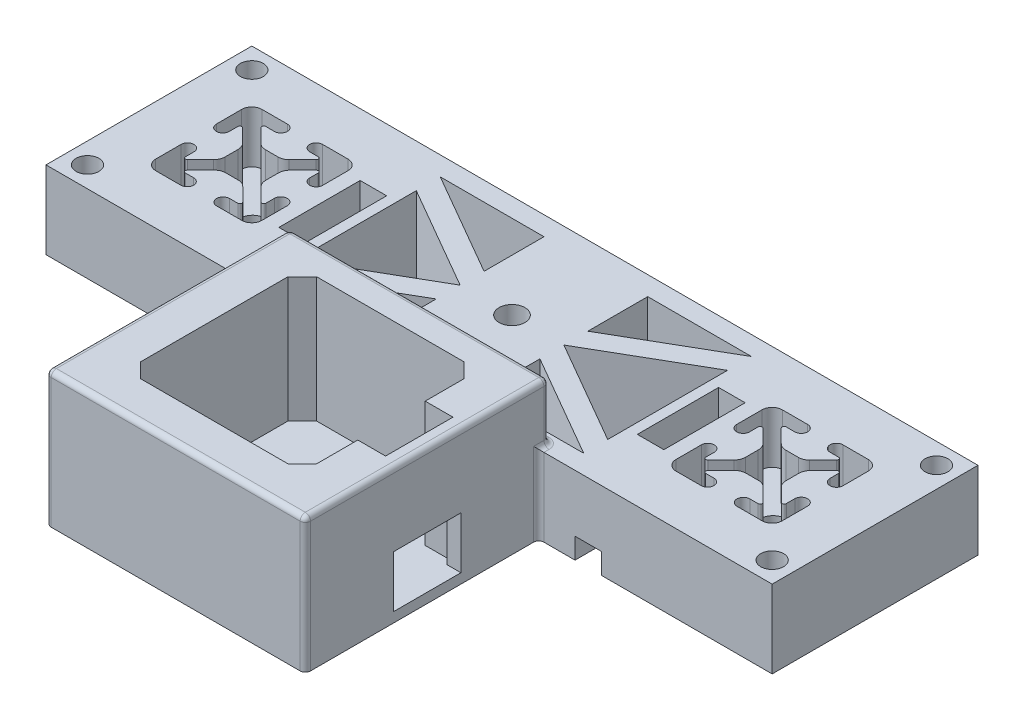
SolidWorks part; units mm, degrees
ref_plane "Front" through (0, 0, 0) normal (0, 0, 1) x (1, 0, 0)
ref_plane "Top" through (0, 0, 0) normal (0, 1, 0) x (1, 0, 0)
ref_plane "Right" through (0, 0, 0) normal (1, 0, 0) x (0, 0, -1)
sketch "Sketch1" plane through (0, 0, 0) normal (0, 1, 0) x (1, 0, 0)
  line L1 (0, 0) -> (177.8, 0)
  line L2 (0, 0) -> (0, 50.4)
  line L3 (0, 50.4) -> (177.8, 50.4)
  line L4 (177.8, 0) -> (177.8, 50.4)
  dimension "D1" = 177.8
  dimension "D2" = 50.4
extrude "Boss-Extrude1" add sketch "Sketch1" along normal blind 6.35
sketch "Sketch2" plane through (0, 6.35, 0) normal (0, 1, 0) x (1, 0, 0)
  line L0 (37.6996, 29.52) -> (37.6996, 35.7372) construction
  line L1 (35.7368, 37.7) -> (29.5196, 37.7) construction
  line L2 (29.5196, 35.56) -> (31.619, 35.56) construction
  line L3 (32.3326, 33.8353) -> (28.9966, 30.504) construction
  line L4 (26.7566, 29.5771) -> (23.643, 29.5771) construction
  line L5 (21.403, 30.504) -> (18.067, 33.8353) construction
  line L6 (18.7806, 35.56) -> (20.88, 35.56) construction
  line L7 (20.88, 37.7) -> (14.6628, 37.7) construction
  line L8 (12.7, 35.7372) -> (12.7, 29.52) construction
  line L9 (14.84, 29.52) -> (14.84, 31.5965) construction
  line L10 (16.5637, 32.3112) -> (19.7659, 29.1135) construction
  line L11 (20.743, 26.7568) -> (20.743, 23.6432) construction
  line L12 (19.7659, 21.2865) -> (16.5637, 18.0888) construction
  line L13 (14.84, 18.8035) -> (14.84, 20.88) construction
  line L14 (12.7, 20.88) -> (12.7, 14.6628) construction
  line L15 (14.6628, 12.7) -> (20.8121, 12.7) construction
  line L16 (20.8121, 14.84) -> (18.7806, 14.84) construction
  line L17 (18.067, 16.5647) -> (21.403, 19.896) construction
  line L18 (23.643, 20.8229) -> (26.7566, 20.8229) construction
  line L19 (28.9966, 19.896) -> (32.3326, 16.5647) construction
  line L20 (31.619, 14.84) -> (29.5875, 14.84) construction
  line L21 (29.5875, 12.7) -> (35.7368, 12.7) construction
  line L22 (37.6996, 14.6628) -> (37.6996, 20.88) construction
  line L23 (35.5596, 20.88) -> (35.5596, 18.8035) construction
  line L24 (33.8359, 18.0888) -> (30.6337, 21.2865) construction
  line L25 (29.6566, 23.6432) -> (29.6566, 26.7568) construction
  line L26 (30.6337, 29.1135) -> (33.8359, 32.3112) construction
  line L27 (35.5596, 31.5965) -> (35.5596, 29.52) construction
  line L28 (0, 50.4) -> (0, 0) construction
  line L29 (177.8, 50.4) -> (0, 50.4) construction
  line L30 (0, 0) -> (177.8, 0) construction
  line L31 (88.9, 50.4) -> (88.9, 0) construction
  line L32 (142.2404, 31.5965) -> (142.2404, 29.52) construction
  line L33 (147.1663, 29.1135) -> (143.9641, 32.3112) construction
  line L34 (148.1434, 23.6432) -> (148.1434, 26.7568) construction
  line L35 (143.9641, 18.0888) -> (147.1663, 21.2865) construction
  line L36 (142.2404, 20.88) -> (142.2404, 18.8035) construction
  line L37 (140.1004, 14.6628) -> (140.1004, 20.88) construction
  line L38 (148.2125, 12.7) -> (142.0632, 12.7) construction
  line L39 (146.181, 14.84) -> (148.2125, 14.84) construction
  line L40 (148.8034, 19.896) -> (145.4674, 16.5647) construction
  line L41 (154.157, 20.8229) -> (151.0434, 20.8229) construction
  line L42 (159.733, 16.5647) -> (156.397, 19.896) construction
  line L43 (156.9879, 14.84) -> (159.0194, 14.84) construction
  line L44 (163.1372, 12.7) -> (156.9879, 12.7) construction
  line L45 (165.1, 20.88) -> (165.1, 14.6628) construction
  line L46 (162.96, 18.8035) -> (162.96, 20.88) construction
  line L47 (158.0341, 21.2865) -> (161.2363, 18.0888) construction
  line L48 (157.057, 26.7568) -> (157.057, 23.6432) construction
  line L49 (161.2363, 32.3112) -> (158.0341, 29.1135) construction
  line L50 (162.96, 29.52) -> (162.96, 31.5965) construction
  line L51 (165.1, 35.7372) -> (165.1, 29.52) construction
  line L52 (156.92, 37.7) -> (163.1372, 37.7) construction
  line L53 (159.0194, 35.56) -> (156.92, 35.56) construction
  line L54 (156.397, 30.504) -> (159.733, 33.8353) construction
  line L55 (151.0434, 29.5771) -> (154.157, 29.5771) construction
  line L56 (145.4674, 33.8353) -> (148.8034, 30.504) construction
  line L57 (148.2804, 35.56) -> (146.181, 35.56) construction
  line L58 (142.0632, 37.7) -> (148.2804, 37.7) construction
  line L59 (140.1004, 29.52) -> (140.1004, 35.7372) construction
  line L60 (38.2076, 29.52) -> (38.2076, 35.7372)
  line L62 (0, 50.4) -> (0, 0)
  line L63 (0, 0) -> (177.8, 0)
  line L64 (177.8, 50.4) -> (177.8, 0)
  line L65 (35.7368, 38.208) -> (29.5196, 38.208)
  line L66 (29.5196, 35.052) -> (31.619, 35.052)
  line L67 (31.9737, 34.1948) -> (28.6376, 30.8635)
  line L68 (26.7566, 30.0851) -> (23.643, 30.0851)
  line L69 (21.762, 30.8635) -> (18.4259, 34.1948)
  line L70 (18.7806, 35.052) -> (20.88, 35.052)
  line L71 (20.88, 38.208) -> (14.6628, 38.208)
  line L72 (12.192, 35.7372) -> (12.192, 29.52)
  line L73 (15.348, 29.52) -> (15.348, 31.5965)
  line L74 (16.2047, 31.9517) -> (19.4069, 28.7541)
  line L75 (20.235, 26.7568) -> (20.235, 23.6432)
  line L76 (19.4069, 21.6459) -> (16.2047, 18.4483)
  line L77 (15.348, 18.8035) -> (15.348, 20.88)
  line L78 (12.192, 20.88) -> (12.192, 14.6628)
  line L79 (14.6628, 12.192) -> (20.8121, 12.192)
  line L80 (20.8121, 15.348) -> (18.7806, 15.348)
  line L81 (18.4259, 16.2052) -> (21.762, 19.5365)
  line L82 (23.643, 20.3149) -> (26.7566, 20.3149)
  line L83 (28.6376, 19.5365) -> (31.9737, 16.2052)
  line L84 (31.619, 15.348) -> (29.5875, 15.348)
  line L85 (29.5875, 12.192) -> (35.7368, 12.192)
  line L86 (38.2076, 14.6628) -> (38.2076, 20.88)
  line L87 (35.0516, 20.88) -> (35.0516, 18.8035)
  line L88 (34.1949, 18.4483) -> (30.9927, 21.6459)
  line L89 (30.1646, 23.6432) -> (30.1646, 26.7568)
  line L90 (30.9927, 28.7541) -> (34.1949, 31.9517)
  line L91 (35.0516, 31.5965) -> (35.0516, 29.52)
  line L92 (142.7484, 31.5965) -> (142.7484, 29.52)
  line L93 (139.5924, 29.52) -> (139.5924, 35.7372)
  line L94 (142.0632, 38.208) -> (148.2804, 38.208)
  line L95 (148.2804, 35.052) -> (146.181, 35.052)
  line L96 (145.8263, 34.1948) -> (149.1624, 30.8635)
  line L97 (151.0434, 30.0851) -> (154.157, 30.0851)
  line L98 (156.038, 30.8635) -> (159.3741, 34.1948)
  line L99 (159.0194, 35.052) -> (156.92, 35.052)
  line L100 (156.92, 38.208) -> (163.1372, 38.208)
  line L101 (165.608, 35.7372) -> (165.608, 29.52)
  line L102 (162.452, 29.52) -> (162.452, 31.5965)
  line L103 (161.5953, 31.9517) -> (158.3931, 28.7541)
  line L104 (157.565, 26.7568) -> (157.565, 23.6432)
  line L105 (158.3931, 21.6459) -> (161.5953, 18.4483)
  line L106 (162.452, 18.8035) -> (162.452, 20.88)
  line L107 (165.608, 20.88) -> (165.608, 14.6628)
  line L108 (163.1372, 12.192) -> (156.9879, 12.192)
  line L109 (156.9879, 15.348) -> (159.0194, 15.348)
  line L110 (159.3741, 16.2052) -> (156.038, 19.5365)
  line L111 (154.157, 20.3149) -> (151.0434, 20.3149)
  line L112 (149.1624, 19.5365) -> (145.8263, 16.2052)
  line L113 (146.181, 15.348) -> (148.2125, 15.348)
  line L114 (148.2125, 12.192) -> (142.0632, 12.192)
  line L115 (139.5924, 14.6628) -> (139.5924, 20.88)
  line L116 (142.7484, 20.88) -> (142.7484, 18.8035)
  line L117 (143.6051, 18.4483) -> (146.8073, 21.6459)
  line L118 (147.6354, 23.6432) -> (147.6354, 26.7568)
  line L119 (146.8073, 28.7541) -> (143.6051, 31.9517)
  line L120 (177.8, 50.4) -> (0, 50.4)
  arc A1 (37.6996, 35.7372) -> (35.7368, 37.7) centre (35.7368, 35.7372) ccw construction
  arc A2 (29.5196, 37.7) -> (29.5196, 35.56) centre (29.5196, 36.63) ccw construction
  arc A3 (31.619, 35.56) -> (32.3326, 33.8353) centre (31.619, 34.55) cw construction
  arc A4 (28.9966, 30.504) -> (26.7566, 29.5771) centre (26.7566, 32.7471) cw construction
  arc A5 (23.643, 29.5771) -> (21.403, 30.504) centre (23.643, 32.7471) cw construction
  arc A6 (18.067, 33.8353) -> (18.7806, 35.56) centre (18.7806, 34.55) cw construction
  arc A7 (20.88, 35.56) -> (20.88, 37.7) centre (20.88, 36.63) ccw construction
  arc A8 (14.6628, 37.7) -> (12.7, 35.7372) centre (14.6628, 35.7372) ccw construction
  arc A9 (12.7, 29.52) -> (14.84, 29.52) centre (13.77, 29.52) ccw construction
  arc A10 (14.84, 31.5965) -> (16.5637, 32.3112) centre (15.85, 31.5965) cw construction
  arc A11 (19.7659, 29.1135) -> (20.743, 26.7568) centre (17.4126, 26.7568) cw construction
  arc A12 (20.743, 23.6432) -> (19.7659, 21.2865) centre (17.4126, 23.6432) cw construction
  arc A13 (16.5637, 18.0888) -> (14.84, 18.8035) centre (15.85, 18.8035) cw construction
  arc A14 (14.84, 20.88) -> (12.7, 20.88) centre (13.77, 20.88) ccw construction
  arc A15 (12.7, 14.6628) -> (14.6628, 12.7) centre (14.6628, 14.6628) ccw construction
  arc A16 (20.8121, 12.7) -> (20.8121, 14.84) centre (20.8121, 13.77) ccw construction
  arc A17 (18.7806, 14.84) -> (18.067, 16.5647) centre (18.7806, 15.85) cw construction
  arc A18 (21.403, 19.896) -> (23.643, 20.8229) centre (23.643, 17.6529) cw construction
  arc A19 (26.7566, 20.8229) -> (28.9966, 19.896) centre (26.7566, 17.6529) cw construction
  arc A20 (32.3326, 16.5647) -> (31.619, 14.84) centre (31.619, 15.85) cw construction
  arc A21 (29.5875, 14.84) -> (29.5875, 12.7) centre (29.5875, 13.77) ccw construction
  arc A22 (35.7368, 12.7) -> (37.6996, 14.6628) centre (35.7368, 14.6628) ccw construction
  arc A23 (37.6996, 20.88) -> (35.5596, 20.88) centre (36.6296, 20.88) ccw construction
  arc A24 (35.5596, 18.8035) -> (33.8359, 18.0888) centre (34.5496, 18.8035) cw construction
  arc A25 (30.6337, 21.2865) -> (29.6566, 23.6432) centre (32.987, 23.6432) cw construction
  arc A26 (29.6566, 26.7568) -> (30.6337, 29.1135) centre (32.987, 26.7568) cw construction
  arc A27 (33.8359, 32.3112) -> (35.5596, 31.5965) centre (34.5496, 31.5965) cw construction
  arc A28 (35.5596, 29.52) -> (37.6996, 29.52) centre (36.6296, 29.52) ccw construction
  arc A29 (142.2404, 29.52) -> (140.1004, 29.52) centre (141.1704, 29.52) cw construction
  arc A30 (143.9641, 32.3112) -> (142.2404, 31.5965) centre (143.2504, 31.5965) ccw construction
  arc A31 (148.1434, 26.7568) -> (147.1663, 29.1135) centre (144.813, 26.7568) ccw construction
  arc A32 (147.1663, 21.2865) -> (148.1434, 23.6432) centre (144.813, 23.6432) ccw construction
  arc A33 (142.2404, 18.8035) -> (143.9641, 18.0888) centre (143.2504, 18.8035) ccw construction
  arc A34 (140.1004, 20.88) -> (142.2404, 20.88) centre (141.1704, 20.88) cw construction
  arc A35 (142.0632, 12.7) -> (140.1004, 14.6628) centre (142.0632, 14.6628) cw construction
  arc A36 (148.2125, 14.84) -> (148.2125, 12.7) centre (148.2125, 13.77) cw construction
  arc A37 (145.4674, 16.5647) -> (146.181, 14.84) centre (146.181, 15.85) ccw construction
  arc A38 (151.0434, 20.8229) -> (148.8034, 19.896) centre (151.0434, 17.6529) ccw construction
  arc A39 (156.397, 19.896) -> (154.157, 20.8229) centre (154.157, 17.6529) ccw construction
  arc A40 (159.0194, 14.84) -> (159.733, 16.5647) centre (159.0194, 15.85) ccw construction
  arc A41 (156.9879, 12.7) -> (156.9879, 14.84) centre (156.9879, 13.77) cw construction
  arc A42 (165.1, 14.6628) -> (163.1372, 12.7) centre (163.1372, 14.6628) cw construction
  arc A43 (162.96, 20.88) -> (165.1, 20.88) centre (164.03, 20.88) cw construction
  arc A44 (161.2363, 18.0888) -> (162.96, 18.8035) centre (161.95, 18.8035) ccw construction
  arc A45 (157.057, 23.6432) -> (158.0341, 21.2865) centre (160.3874, 23.6432) ccw construction
  arc A46 (158.0341, 29.1135) -> (157.057, 26.7568) centre (160.3874, 26.7568) ccw construction
  arc A47 (162.96, 31.5965) -> (161.2363, 32.3112) centre (161.95, 31.5965) ccw construction
  arc A48 (165.1, 29.52) -> (162.96, 29.52) centre (164.03, 29.52) cw construction
  arc A49 (163.1372, 37.7) -> (165.1, 35.7372) centre (163.1372, 35.7372) cw construction
  arc A50 (156.92, 35.56) -> (156.92, 37.7) centre (156.92, 36.63) cw construction
  arc A51 (159.733, 33.8353) -> (159.0194, 35.56) centre (159.0194, 34.55) ccw construction
  arc A52 (154.157, 29.5771) -> (156.397, 30.504) centre (154.157, 32.7471) ccw construction
  arc A53 (148.8034, 30.504) -> (151.0434, 29.5771) centre (151.0434, 32.7471) ccw construction
  arc A54 (146.181, 35.56) -> (145.4674, 33.8353) centre (146.181, 34.55) ccw construction
  arc A55 (148.2804, 37.7) -> (148.2804, 35.56) centre (148.2804, 36.63) cw construction
  arc A56 (140.1004, 35.7372) -> (142.0632, 37.7) centre (142.0632, 35.7372) cw construction
  arc A58 (38.2076, 35.7372) -> (35.7368, 38.208) centre (35.7368, 35.7372) ccw
  arc A59 (29.5196, 38.208) -> (29.5196, 35.052) centre (29.5196, 36.63) ccw
  arc A60 (31.619, 35.052) -> (31.9737, 34.1948) centre (31.619, 34.55) cw
  arc A61 (28.6376, 30.8635) -> (26.7566, 30.0851) centre (26.7566, 32.7471) cw
  arc A62 (23.643, 30.0851) -> (21.762, 30.8635) centre (23.643, 32.7471) cw
  arc A63 (18.4259, 34.1948) -> (18.7806, 35.052) centre (18.7806, 34.55) cw
  arc A64 (20.88, 35.052) -> (20.88, 38.208) centre (20.88, 36.63) ccw
  arc A65 (14.6628, 38.208) -> (12.192, 35.7372) centre (14.6628, 35.7372) ccw
  arc A66 (12.192, 29.52) -> (15.348, 29.52) centre (13.77, 29.52) ccw
  arc A67 (15.348, 31.5965) -> (16.2047, 31.9517) centre (15.85, 31.5965) cw
  arc A68 (19.4069, 28.7541) -> (20.235, 26.7568) centre (17.4126, 26.7568) cw
  arc A69 (20.235, 23.6432) -> (19.4069, 21.6459) centre (17.4126, 23.6432) cw
  arc A70 (16.2047, 18.4483) -> (15.348, 18.8035) centre (15.85, 18.8035) cw
  arc A71 (15.348, 20.88) -> (12.192, 20.88) centre (13.77, 20.88) ccw
  arc A72 (12.192, 14.6628) -> (14.6628, 12.192) centre (14.6628, 14.6628) ccw
  arc A73 (20.8121, 12.192) -> (20.8121, 15.348) centre (20.8121, 13.77) ccw
  arc A74 (18.7806, 15.348) -> (18.4259, 16.2052) centre (18.7806, 15.85) cw
  arc A75 (21.762, 19.5365) -> (23.643, 20.3149) centre (23.643, 17.6529) cw
  arc A76 (26.7566, 20.3149) -> (28.6376, 19.5365) centre (26.7566, 17.6529) cw
  arc A77 (31.9737, 16.2052) -> (31.619, 15.348) centre (31.619, 15.85) cw
  arc A78 (29.5875, 15.348) -> (29.5875, 12.192) centre (29.5875, 13.77) ccw
  arc A79 (35.7368, 12.192) -> (38.2076, 14.6628) centre (35.7368, 14.6628) ccw
  arc A80 (38.2076, 20.88) -> (35.0516, 20.88) centre (36.6296, 20.88) ccw
  arc A81 (35.0516, 18.8035) -> (34.1949, 18.4483) centre (34.5496, 18.8035) cw
  arc A82 (30.9927, 21.6459) -> (30.1646, 23.6432) centre (32.987, 23.6432) cw
  arc A83 (30.1646, 26.7568) -> (30.9927, 28.7541) centre (32.987, 26.7568) cw
  arc A84 (34.1949, 31.9517) -> (35.0516, 31.5965) centre (34.5496, 31.5965) cw
  arc A85 (35.0516, 29.52) -> (38.2076, 29.52) centre (36.6296, 29.52) ccw
  arc A86 (142.7484, 29.52) -> (139.5924, 29.52) centre (141.1704, 29.52) cw
  arc A87 (139.5924, 35.7372) -> (142.0632, 38.208) centre (142.0632, 35.7372) cw
  arc A88 (148.2804, 38.208) -> (148.2804, 35.052) centre (148.2804, 36.63) cw
  arc A89 (146.181, 35.052) -> (145.8263, 34.1948) centre (146.181, 34.55) ccw
  arc A90 (149.1624, 30.8635) -> (151.0434, 30.0851) centre (151.0434, 32.7471) ccw
  arc A91 (154.157, 30.0851) -> (156.038, 30.8635) centre (154.157, 32.7471) ccw
  arc A92 (159.3741, 34.1948) -> (159.0194, 35.052) centre (159.0194, 34.55) ccw
  arc A93 (156.92, 35.052) -> (156.92, 38.208) centre (156.92, 36.63) cw
  arc A94 (163.1372, 38.208) -> (165.608, 35.7372) centre (163.1372, 35.7372) cw
  arc A95 (165.608, 29.52) -> (162.452, 29.52) centre (164.03, 29.52) cw
  arc A96 (162.452, 31.5965) -> (161.5953, 31.9517) centre (161.95, 31.5965) ccw
  arc A97 (158.3931, 28.7541) -> (157.565, 26.7568) centre (160.3874, 26.7568) ccw
  arc A98 (157.565, 23.6432) -> (158.3931, 21.6459) centre (160.3874, 23.6432) ccw
  arc A99 (161.5953, 18.4483) -> (162.452, 18.8035) centre (161.95, 18.8035) ccw
  arc A100 (162.452, 20.88) -> (165.608, 20.88) centre (164.03, 20.88) cw
  arc A101 (165.608, 14.6628) -> (163.1372, 12.192) centre (163.1372, 14.6628) cw
  arc A102 (156.9879, 12.192) -> (156.9879, 15.348) centre (156.9879, 13.77) cw
  arc A103 (159.0194, 15.348) -> (159.3741, 16.2052) centre (159.0194, 15.85) ccw
  arc A104 (156.038, 19.5365) -> (154.157, 20.3149) centre (154.157, 17.6529) ccw
  arc A105 (151.0434, 20.3149) -> (149.1624, 19.5365) centre (151.0434, 17.6529) ccw
  arc A106 (145.8263, 16.2052) -> (146.181, 15.348) centre (146.181, 15.85) ccw
  arc A107 (148.2125, 15.348) -> (148.2125, 12.192) centre (148.2125, 13.77) cw
  arc A108 (142.0632, 12.192) -> (139.5924, 14.6628) centre (142.0632, 14.6628) cw
  arc A109 (139.5924, 20.88) -> (142.7484, 20.88) centre (141.1704, 20.88) cw
  arc A110 (142.7484, 18.8035) -> (143.6051, 18.4483) centre (143.2504, 18.8035) ccw
  arc A111 (146.8073, 21.6459) -> (147.6354, 23.6432) centre (144.813, 23.6432) ccw
  arc A112 (147.6354, 26.7568) -> (146.8073, 28.7541) centre (144.813, 26.7568) ccw
  arc A113 (143.6051, 31.9517) -> (142.7484, 31.5965) centre (143.2504, 31.5965) ccw
  dimension "D2" = 1.07
  dimension "D3" = 3.17
  dimension "D4" = 3.3305
  dimension "D8" = 1.9628
  dimension "D9" = 1.01
  dimension "D5" = 12.7
  dimension "D6" = 12.7
  dimension "D7" = 12.7
  dimension "D10" = 16.5637
  dimension "D12" = 0.508
  dimension "D13" = 0.508
extrude "Boss-Extrude2" add sketch "Sketch2" along normal blind 12.7
sketch "Sketch3" plane through (0, 19.05, 0) normal (0, 1, 0) x (1, 0, 0)
  line L0 (177.8, 50.4) -> (0, 50.4) construction
  line L1 (0, 50.4) -> (0, 0) construction
  circle A0 centre (88.9, 25.2) radius 3.175
  point P4 (88.9, 50.4)
  point P7 (0, 25.2)
  dimension "D1" = 6.35
extrude "Cut-Extrude1" cut sketch "Sketch3" against normal through all
sketch "Sketch4" plane through (0, 19.05, 0) normal (0, 1, 0) x (1, 0, 0)
  line L0 (50.8, 45.7306) -> (76.2, 45.7306)
  line L1 (76.2, 45.7306) -> (76.2, 31.0659)
  line L2 (76.2, 31.0659) -> (50.8, 45.7306)
  line L3 (76.2, 19.3341) -> (76.2, 4.6694)
  line L4 (76.2, 4.6694) -> (50.8, 4.6694)
  line L5 (50.8, 4.6694) -> (76.2, 19.3341)
  line L6 (50.8, 39.8647) -> (50.8, 10.5353)
  line L7 (50.8, 10.5353) -> (76.2, 25.2)
  line L8 (76.2, 25.2) -> (50.8, 39.8647)
  line L9 (0, 50.4) -> (0, 0) construction
  line L10 (88.9, 50.4) -> (88.9, 0) construction
  line L11 (177.8, 50.4) -> (0, 50.4) construction
  line L12 (0, 0) -> (177.8, 0) construction
  line L13 (101.6, 25.2) -> (127, 39.8647)
  line L14 (127, 10.5353) -> (101.6, 25.2)
  line L15 (127, 39.8647) -> (127, 10.5353)
  line L16 (127, 4.6694) -> (101.6, 19.3341)
  line L17 (101.6, 4.6694) -> (127, 4.6694)
  line L18 (101.6, 19.3341) -> (101.6, 4.6694)
  line L19 (101.6, 31.0659) -> (127, 45.7306)
  line L20 (101.6, 45.7306) -> (101.6, 31.0659)
  line L21 (127, 45.7306) -> (101.6, 45.7306)
  point P18 (88.9, 25.2)
  dimension "D1" = 25.4
  dimension "D2" = 25.4
  dimension "D3" = 50.8
  dimension "D4" = 5.08
  dimension "D5" = 5.08
  dimension "D7" = 60
extrude "Cut-Extrude2" cut sketch "Sketch4" against normal through all
sketch "Sketch5" plane through (0, 19.05, 0) normal (0, 1, 0) x (1, 0, 0)
  line L0 (0, 50.4) -> (0, 0) construction
  line L1 (41.7636, 35.15) -> (48.2636, 35.15)
  line L2 (41.7636, 35.15) -> (41.7636, 15.25)
  line L3 (41.7636, 15.25) -> (48.2636, 15.25)
  line L4 (48.2636, 35.15) -> (48.2636, 15.25)
  line L5 (38.2076, 29.52) -> (38.2076, 35.7372) construction
  point P6 (0, 25.2)
  point P7 (48.2636, 25.2)
  dimension "D1" = 6.5
  dimension "D2" = 19.9
  dimension "D3" = 3.556
extrude "Cut-Extrude3" cut sketch "Sketch5" against normal blind 10.2
sketch "Sketch6" plane through (0, 8.85, 0) normal (0, 1, 0) x (1, 0, 0)
  line L0 (48.2636, 15.25) -> (48.2636, 35.15) construction
  line L1 (41.7636, 35.15) -> (48.2636, 35.15)
  line L2 (41.7636, 35.15) -> (41.7636, 30.578)
  line L3 (41.7636, 30.578) -> (48.2636, 30.578)
  line L4 (48.2636, 35.15) -> (48.2636, 30.578)
  line L5 (41.7636, 35.15) -> (41.7636, 15.25) construction
  line L6 (48.2636, 15.25) -> (48.2636, 35.15) construction
  line L7 (41.7636, 27.486) -> (48.2636, 27.486)
  line L8 (41.7636, 27.486) -> (41.7636, 22.914)
  line L9 (41.7636, 22.914) -> (48.2636, 22.914)
  line L10 (48.2636, 27.486) -> (48.2636, 22.914)
  line L12 (41.7636, 15.25) -> (48.2636, 15.25)
  line L13 (41.7636, 15.25) -> (41.7636, 19.822)
  line L14 (41.7636, 19.822) -> (48.2636, 19.822)
  line L15 (48.2636, 15.25) -> (48.2636, 19.822)
  line L16 (41.7636, 25.2) -> (0, 25.2) construction
  line L17 (0, 50.4) -> (0, 0) construction
  dimension "D1" = 4.572
extrude "Cut-Extrude4" cut sketch "Sketch6" against normal through all
ref_plane "Plane1" through (88.9, 0, 0) normal (-1, 0, 0) x (0, 0, 1)
mirror "Mirror1" about plane through (88.9, 0, 0) normal (-1, 0, 0) of "Cut-Extrude4", "Cut-Extrude3"
sketch "Sketch7" plane through (0, 6.35, 0) normal (0, 1, 0) x (1, 0, 0)
  line L0 (26.7566, 30.0851) -> (23.643, 30.0851) construction
  line L1 (30.1646, 23.6432) -> (30.1646, 26.7568) construction
  circle A0 centre (25.3386, 25.2591) radius 2.921
  dimension "D1" = 5.842
  dimension "D2" = 4.826
  dimension "D3" = 4.826
extrude "Cut-Extrude5" cut sketch "Sketch7" against normal through all both and the other way through all
sketch "Sketch8" plane through (0, 6.35, 0) normal (0, 1, 0) x (1, 0, 0)
  line L0 (154.157, 30.0851) -> (151.0434, 30.0851) construction
  line L1 (157.565, 23.6432) -> (157.565, 26.7568) construction
  circle A0 centre (152.739, 25.2591) radius 2.921
  dimension "D1" = 5.842
  dimension "D2" = 4.826
  dimension "D3" = 4.826
extrude "Cut-Extrude6" cut sketch "Sketch8" against normal through all both and the other way through all
chamfer "Chamfer2" distance 3.302 angle 45 1 edges at (152.739, 0, -22.3381)
chamfer "Chamfer3" distance 3.302 angle 45 1 edges at (25.3386, 0, -22.3381)
sketch "Sketch9" plane through (0, 0, 0) normal (0, 1, 0) x (1, 0, 0)
  line L0 (120.65, 0) -> (120.65, -57.15)
  line L3 (0, 0) -> (177.8, 0) construction
  line L8 (57.15, -57.15) -> (120.65, -57.15)
  line L13 (57.15, 0) -> (57.15, -57.15)
  line L15 (57.15, 0) -> (57.15, 2.54)
  line L16 (57.15, 2.54) -> (120.65, 2.54)
  line L17 (120.65, 0) -> (120.65, 2.54)
  dimension "D1" = 57.15
  dimension "D2" = 63.5
  dimension "D3" = 2.54
sketch "Sketch11" plane through (0, 0, 0) normal (0, 1, 0) x (1, 0, 0)
  line L0 (0, 0) -> (177.8, 0) construction
  line L2 (41.7636, 15.25) -> (41.7636, 0)
  line L3 (41.7636, 0) -> (48.2636, 0)
  line L4 (48.2636, 15.25) -> (48.2636, 0)
  line L5 (48.2636, 15.25) -> (48.2636, 35.15) construction
  line L6 (177.8, 50.4) -> (0, 50.4) construction
  line L8 (41.7636, 35.15) -> (41.7636, 50.4)
  line L9 (41.7636, 50.4) -> (48.2636, 50.4)
  line L10 (48.2636, 35.15) -> (48.2636, 50.4)
  line L11 (41.7636, 35.15) -> (41.7636, 15.25)
  line L12 (48.2636, 35.15) -> (48.2636, 15.25)
  line L13 (88.9, 50.4) -> (88.9, 0) construction
  line L14 (136.0364, 0) -> (129.5364, 0)
  line L15 (136.0364, 50.4) -> (129.5364, 50.4)
  line L16 (129.5364, 15.25) -> (129.5364, 0)
  line L17 (136.0364, 15.25) -> (136.0364, 0)
  line L18 (129.5364, 35.15) -> (129.5364, 15.25)
  line L19 (136.0364, 35.15) -> (136.0364, 15.25)
  line L20 (129.5364, 35.15) -> (129.5364, 50.4)
  line L21 (136.0364, 35.15) -> (136.0364, 50.4)
extrude "Cut-Extrude8" cut sketch "Sketch11" along normal blind 5.08
extrude "Boss-Extrude4" add sketch "Sketch9" along normal blind 33.02
sketch "Sketch12" plane through (0, 33.02, 0) normal (0, 1, 0) x (1, 0, 0)
  line L0 (70.8455, -4.556) -> (106.9545, -4.556)
  line L1 (106.9545, -4.556) -> (110.49, -8.0915)
  line L2 (110.49, -8.0915) -> (110.49, -17.642)
  line L3 (110.49, -44.2005) -> (106.9545, -47.736)
  line L4 (106.9545, -47.736) -> (70.8455, -47.736)
  line L5 (70.8455, -47.736) -> (67.31, -44.2005)
  line L6 (67.31, -44.2005) -> (67.31, -8.0915)
  line L7 (67.31, -8.0915) -> (70.8455, -4.556)
  line L8 (57.15, -57.15) -> (120.65, -57.15) construction
  line L9 (85.725, 25.2) -> (92.075, 25.2) construction
  line L10 (110.49, -34.142) -> (110.49, -44.2005)
  line L11 (110.49, -17.642) -> (117.29, -17.642)
  line L13 (110.49, -34.142) -> (117.29, -34.142)
  line L14 (117.29, -17.642) -> (117.29, -34.142)
  circle A0 centre (88.9, 25.2) radius 3.175 construction
  point P10 (88.9, -57.15)
  point P11 (88.9, -47.736)
  point P15 (67.31, -26.146)
  dimension "D9" = 51.346
  dimension "D1" = 5
  dimension "D2" = 43.18
  dimension "D3" = 135
  dimension "D4" = 135
  dimension "D5" = 135
  dimension "D6" = 43.18
  dimension "D7" = 16.5
  dimension "D8" = 6.8
extrude "Cut-Extrude9" cut sketch "Sketch12" against normal blind 30.6
sketch "Sketch13" plane through (120.65, 0, 0) normal (1, 0, 0) x (0, 0, -1)
  line L0 (-57.15, 33.02) -> (2.54, 33.02) construction
  line L1 (-35.555, 15.12) -> (-19.055, 15.12)
  line L2 (-35.555, 15.12) -> (-35.555, 2.42)
  line L3 (-35.555, 2.42) -> (-19.055, 2.42)
  line L4 (-19.055, 15.12) -> (-19.055, 2.42)
  point P6 (-27.305, 33.02)
  point P7 (-27.305, 15.12)
  dimension "D1" = 16.5
  dimension "D2" = 12.7
  dimension "D3" = 30.6
extrude "Cut-Extrude10" cut sketch "Sketch13" against normal blind 30.6
fillet "Fillet1" radius 1.27 13 edges at (120.65, 19.05, -1.27) (57.15, 19.05, -1.27) (120.65, 26.035, -2.54) (57.15, 26.035, -2.54) (88.9, 19.05, -2.54) (57.15, 9.525, 0) (120.65, 9.525, 0) (120.65, 33.02, 27.305) (120.65, 16.51, 57.15) (88.9, 33.02, 57.15) (57.15, 33.02, 27.305) (57.15, 16.51, 57.15) (88.9, 33.02, -2.54)
sketch "Sketch14" plane through (0, 2.42, 0) normal (0, 1, 0) x (1, 0, 0)
  line L0 (88.9, -4.556) -> (88.9, -47.736) construction
  line L1 (106.9545, -4.556) -> (70.8455, -4.556) construction
  line L2 (70.8455, -47.736) -> (106.9545, -47.736) construction
  circle A0 centre (88.9, -26.146) radius 2.921
  dimension "D1" = 5.842
extrude "Cut-Extrude11" cut sketch "Sketch14" against normal through all
sketch "Sketch15" plane through (0, 0, 0) normal (0, 1, 0) x (1, 0, 0)
  circle A0 centre (88.9, 25.2) radius 10.16
  dimension "D1" = 20.32
extrude "Cut-Extrude12" cut sketch "Sketch15" along normal blind 8.128
sketch "Sketch16" plane through (0, 19.05, 0) normal (0, 1, 0) x (1, 0, 0)
  line L0 (88.9, 50.4) -> (88.9, -47.736) construction
  line L1 (177.8, 50.4) -> (0, 50.4) construction
  line L2 (70.8455, -47.736) -> (106.9545, -47.736) construction
  line L3 (0, 25.2) -> (177.8, 25.2) construction
  line L4 (0, 50.4) -> (0, 0) construction
  line L5 (177.8, 0) -> (177.8, 50.4) construction
  circle A0 centre (5.08, 45.32) radius 2.794
  circle A1 centre (5.08, 5.08) radius 2.794
  circle A2 centre (172.72, 5.08) radius 2.794
  circle A3 centre (172.72, 45.32) radius 2.794
  dimension "D1" = 5.588
  dimension "D3" = 5.08
  dimension "D2" = 5.08
extrude "Cut-Extrude13" cut sketch "Sketch16" against normal through all
